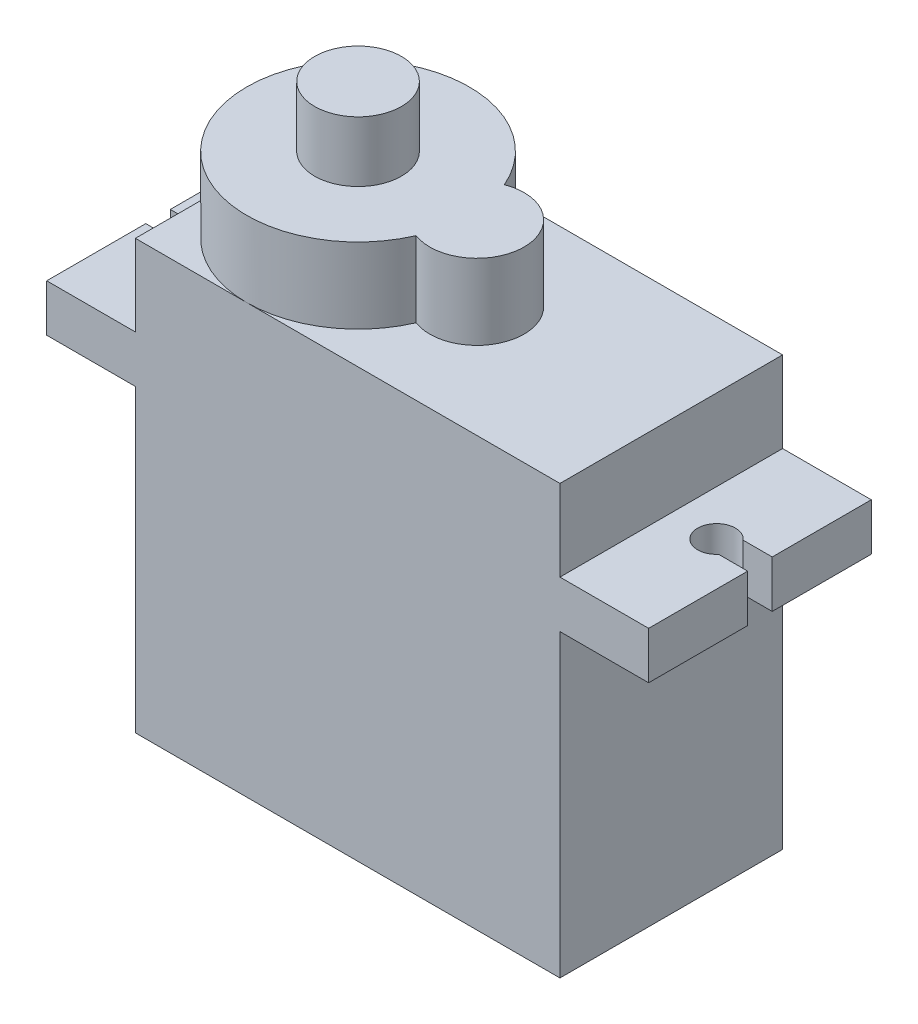
SolidWorks part; units mm, degrees
ref_plane "Front Plane" through (0, 0, 0) normal (0, 0, 1) x (1, 0, 0)
ref_plane "Top Plane" through (0, 0, 0) normal (0, 1, 0) x (1, 0, 0)
ref_plane "Right Plane" through (0, 0, 0) normal (1, 0, 0) x (0, 0, -1)
sketch "Sketch1" plane through (0, 0, 0) normal (0, 1, 0) x (1, 0, 0)
  line L1 (-11.25, 5.9) -> (11.25, 5.9)
  line L2 (-11.25, 5.9) -> (-11.25, -5.9)
  line L3 (-11.25, -5.9) -> (11.25, -5.9)
  line L4 (11.25, 5.9) -> (11.25, -5.9)
  line L5 (-11.25, 5.9) -> (11.25, -5.9) construction
  line L6 (-11.25, -5.9) -> (11.25, 5.9) construction
  point P0 (0, 0)
  dimension "D1" = 11.8
  dimension "D2" = 22.5
extrude "Boss-Extrude1" add sketch "Sketch1" along normal blind 22.7
sketch "Sketch2" plane through (0, 0, 0) normal (0, 1, 0) x (1, 0, 0)
  line L0 (11.25, 5.9) -> (-11.25, 5.9) construction
  line L1 (-15.95, 5.9) -> (15.95, 5.9)
  line L2 (-15.95, 5.9) -> (-15.95, -5.9)
  line L3 (-15.95, -5.9) -> (15.95, -5.9)
  line L4 (15.95, 5.9) -> (15.95, -5.9)
  line L5 (-15.95, 5.9) -> (15.95, -5.9) construction
  line L6 (-15.95, -5.9) -> (15.95, 5.9) construction
  line L7 (11.25, -5.9) -> (11.25, 5.9) construction
  point P0 (0, 0)
  dimension "D1" = 4.7
extrude "Boss-Extrude2" add sketch "Sketch2" along normal blind 2.5 from offset 15.9
sketch "Sketch3" plane through (0, 18.4, 0) normal (0, 1, 0) x (1, 0, 0)
  line L0 (-13.65, 5.9) -> (-13.65, 0) construction
  line L1 (-11.25, 5.9) -> (-15.95, 5.9) construction
  line L2 (-15.95, 0) -> (-13.65, 0) construction
  line L3 (-15.95, 5.9) -> (-15.95, -5.9) construction
  line L4 (-15.95, 0.65) -> (-14.4099, 0.65)
  line L5 (-15.95, -0.65) -> (-14.4099, -0.65)
  line L6 (0, 5.9) -> (0, -5.9) construction
  line L9 (15.95, 0) -> (13.65, 0) construction
  line L10 (13.65, 5.9) -> (13.65, 0) construction
  line L11 (15.95, -0.65) -> (14.4099, -0.65)
  line L12 (15.95, 0.65) -> (14.4099, 0.65)
  line L13 (-15.95, 0.65) -> (-15.95, -0.65)
  circle A0 centre (-13.65, 0) radius 1
  circle A1 centre (13.65, 0) radius 1
  line M8 (15.95, -5.9) -> (15.95, 5.9)
  dimension "D4" = 2
  dimension "D1" = 5.9
  dimension "D2" = 2.3
  dimension "D3" = 1.3
extrude "Cut-Extrude1" cut sketch "Sketch3" against normal through all contours A0 L4 L13 L5 | A0 | A1 | L12 A1 L11 M8 region at (-15.2603, 18.4, 0) region at (-13.65, 18.4, 0) region at (15.2603, 18.4, 0) region at (13.65, 18.4, 0)
sketch "Sketch4" plane through (0, 22.7, 0) normal (0, 1, 0) x (1, 0, 0)
  line L0 (-11.25, 5.9) -> (-11.25, -5.9) construction
  line L1 (11.25, 5.9) -> (-11.25, 5.9) construction
  line L2 (-11.25, -5.9) -> (11.25, -5.9) construction
  line L3 (0.95, 2.5) -> (-0.0058, 2.5)
  line L4 (0.95, -2.5) -> (-0.0058, -2.5)
  line L5 (-5.35, 0) -> (0.95, 0) construction
  line L6 (0.95, 2.5) -> (0.95, -2.5) construction
  line L7 (3.45, 0) -> (0.95, 0) construction
  circle A0 centre (-5.35, 0) radius 5.9
  circle A1 centre (-5.35, 0) radius 2.3
  circle A2 centre (0.95, 0) radius 2.5
  dimension "D1" = 4.6
  dimension "D2" = 5
  dimension "D3" = 8.8
extrude "Boss-Extrude3" add sketch "Sketch4" along normal blind 4 contours A2 A0 A1 | A2 A0 | A0 A2 region at (1.7088, 22.7, 0) region at (-0.1181, 22.7, -2.3526) region at (-0.4152, 22.7, 0)
extrude "Boss-Extrude4" add sketch "Sketch4<3>" along normal blind 7.2 contours A1 region at (-5.35, 22.7, 0)
sketch "Sketch4<3>" plane through (0, 22.7, 0) normal (0, 1, 0) x (1, 0, 0) same geometry as "Sketch4"
sketch "Sketch5" plane through (-11.25, 0, 0) normal (-1, 0, 0) x (0, 0, 1)
  line L0 (0, 4.5) -> (0, 0) construction
  line L1 (-1.8, 5.7) -> (1.8, 5.7)
  line L2 (-1.8, 5.7) -> (-1.8, 4.5)
  line L3 (-1.8, 4.5) -> (1.8, 4.5)
  line L4 (1.8, 5.7) -> (1.8, 4.5)
  line L5 (-1.8, 5.7) -> (1.8, 4.5) construction
  line L6 (-1.8, 4.5) -> (1.8, 5.7) construction
  line L7 (-5.9, 0) -> (5.9, 0) construction
  point P0 (0, 5.1)
  dimension "D1" = 4.5
  dimension "D2" = 3.6
  dimension "D3" = 1.2
extrude "Cut-Extrude2" cut sketch "Sketch5" against normal blind 4
